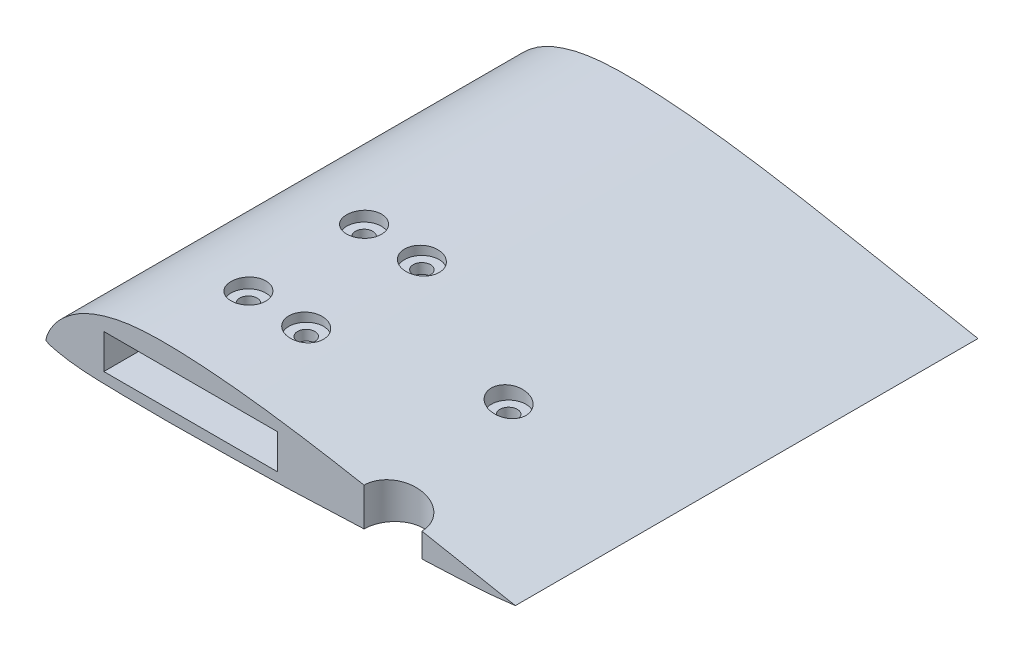
SolidWorks part; units mm, degrees
ref_plane "Front Plane" through (0, 0, 0) normal (0, 0, 1) x (1, 0, 0)
ref_plane "Top Plane" through (0, 0, 0) normal (0, 1, 0) x (1, 0, 0)
ref_plane "Right Plane" through (0, 0, 0) normal (1, 0, 0) x (0, 0, -1)
sketch "Sketch1" plane through (0, 0, 0) normal (0, 0, 1) x (1, 0, 0)
  line L0 (-18.4254, -0.1994) -> (62.7428, 0.679) construction
  line L1 (0, 9.7117) -> (0, -1.7957) construction
  line L2 (0, 9.741) -> (57.212, 9.741) construction
  line L3 (-32.1621, -1.8069) -> (66.409, -1.8069) construction
  spline S0 degree 3 poles (-18.4254, -0.1994) (-18.2508, -0.3232) (-18.0613, -0.4258) (-17.6702, -0.5885) (-17.4657, -0.6456) (-17.0528, -0.749) (-16.8454, -0.7957) (-16.4304, -0.8873) (-16.2225, -0.931) (-15.1812, -1.1388) (-14.3413, -1.2671) (-12.6506, -1.4595) (-11.8043, -1.5245) (-10.1107, -1.6203) (-9.2634, -1.6518) (-7.5684, -1.6982) (-6.7206, -1.7128) (-5.0249, -1.7383) (-4.1771, -1.7502) (-1.6335, -1.7827) (0.0625, -1.7998) (3.4549, -1.8108) (5.1508, -1.8016) (8.542, -1.7594) (10.2375, -1.7325) (13.6285, -1.6815) (15.3239, -1.6542) (18.7145, -1.5852) (20.4097, -1.5422) (25.4944, -1.3858) (28.8835, -1.2519) (33.967, -1.0399) (35.6612, -0.9657) (39.0492, -0.8072) (40.7428, -0.7213) (44.1297, -0.5456) (45.8232, -0.4567) (48.3639, -0.3343) (49.2109, -0.2955) (50.9053, -0.2226) (51.7526, -0.1878) (54.2939, -0.0756) (55.9876, 0.0095) (58.524, 0.2057) (59.3687, 0.2835) (61.0566, 0.4667) (61.8999, 0.5704) (62.7428, 0.679) knots 0 0 0 0 0.007813 0.007813 0.015625 0.015625 0.023438 0.023438 0.03125 0.03125 0.0625 0.0625 0.09375 0.09375 0.125 0.125 0.15625 0.15625 0.1875 0.1875 0.25 0.25 0.3125 0.3125 0.375 0.375 0.4375 0.4375 0.5 0.5 0.625 0.625 0.6875 0.6875 0.75 0.75 0.8125 0.8125 0.84375 0.84375 0.875 0.875 0.9375 0.9375 0.96875 0.96875 1 1 1 1
  spline S1 degree 3 poles (62.7428, 0.679) (59.228, 1.3467) (55.713, 2.013) (48.6835, 3.3493) (45.1699, 4.023) (38.1396, 5.3544) (34.6234, 6.0144) (27.5735, 7.2391) (24.0376, 7.8013) (16.9447, 8.7559) (13.3876, 9.1503) (8.0325, 9.5463) (6.2468, 9.646) (2.6732, 9.7541) (0.8855, 9.763) (-1.7993, 9.6315) (-2.6938, 9.5629) (-4.4662, 9.3564) (-5.3455, 9.2179) (-7.0877, 8.8546) (-7.9506, 8.6308) (-9.2314, 8.2238) (-9.6572, 8.0759) (-10.4962, 7.7567) (-11.3226, 7.4137) (-12.1183, 7.0123) (-12.8953, 6.5754) (-13.2746, 6.3395) (-14.0157, 5.8346) (-14.3793, 5.5647) (-15.0778, 4.9993) (-15.4131, 4.703) (-16.0517, 4.0791) (-16.3556, 3.752) (-16.9211, 3.0566) (-17.1818, 2.684) (-17.5376, 2.1057) (-17.6507, 1.9099) (-17.8667, 1.5129) (-17.9691, 1.3114) (-18.1538, 0.8974) (-18.2363, 0.6841) (-18.3633, 0.2503) (-18.4082, 0.0288) (-18.4254, -0.1994) knots 0 0 0 0 0.125 0.125 0.25 0.25 0.375 0.375 0.5 0.5 0.625 0.625 0.6875 0.6875 0.75 0.75 0.78125 0.78125 0.8125 0.8125 0.84375 0.84375 0.859375 0.859375 0.875 0.890625 0.890625 0.90625 0.90625 0.921875 0.921875 0.9375 0.9375 0.953125 0.953125 0.96875 0.96875 0.976562 0.976562 0.984375 0.984375 0.992188 0.992188 1 1 1 1
  point P4 (0, 0)
  dimension "D1" = 81.1682
  dimension "D2" = 11.5074
extrude "Boss-Extrude1" add sketch "Sketch1" along normal blind 80
sketch "Sketch2" plane through (0, 0, 80) normal (0, 0, 1) x (1, 0, 0)
  line L0 (-35.2815, 9.741) -> (70.1163, 9.741) construction
  line L1 (-36.5718, -1.8069) -> (68.6648, -1.8069) construction
  line L2 (-20.4254, 9.741) -> (-20.4254, -1.8069) construction
  line L3 (-8.4254, 9.741) -> (-8.4254, -1.6748) construction
  line L4 (-18.4254, -0.1994) -> (-20.4254, -0.1994) construction
  line L5 (-8.4254, 6.1531) -> (-8.4254, 0.1531)
  line L6 (-8.4254, 6.1531) -> (21.5746, 6.1531)
  line L7 (-8.4254, 0.1531) -> (21.5746, 0.1531)
  line L8 (21.5746, 6.1531) -> (21.5746, 0.1531)
  spline S2 degree 3 poles (552.4176, -2863.2339) (715.2007, -106.4952) (382.2094, -60.0531) (48.6835, 3.3493) (45.1699, 4.023) (38.1396, 5.3544) (34.6234, 6.0144) (27.5735, 7.2391) (24.0376, 7.8013) (16.9447, 8.7559) (13.3876, 9.1503) (8.0325, 9.5463) (6.2468, 9.646) (2.6732, 9.7541) (0.8855, 9.763) (-1.7993, 9.6315) (-2.6938, 9.5629) (-4.4662, 9.3564) (-5.3455, 9.2179) (-7.0877, 8.8546) (-7.9506, 8.6308) (-9.2314, 8.2238) (-9.6572, 8.0759) (-10.4962, 7.7567) (-11.3226, 7.4137) (-12.1183, 7.0123) (-12.8953, 6.5754) (-13.2746, 6.3395) (-14.0157, 5.8346) (-14.3793, 5.5647) (-15.0778, 4.9993) (-15.4131, 4.703) (-16.0517, 4.0791) (-16.3556, 3.752) (-16.9211, 3.0566) (-17.1818, 2.684) (-17.5376, 2.1057) (-17.6507, 1.9099) (-17.8667, 1.5129) (-17.9691, 1.3114) (-18.1538, 0.8974) (-18.2363, 0.6841) (-22.5005, -13.8816) (54.4548, -48.0097) (2883.2922, -752.8251) knots -11.611785 -11.611785 -11.611785 -11.611785 0.125 0.125 0.25 0.25 0.375 0.375 0.5 0.5 0.625 0.625 0.6875 0.6875 0.75 0.75 0.78125 0.78125 0.8125 0.8125 0.84375 0.84375 0.859375 0.859375 0.875 0.890625 0.890625 0.90625 0.90625 0.921875 0.921875 0.9375 0.9375 0.953125 0.953125 0.96875 0.96875 0.976562 0.976562 0.984375 0.984375 0.992188 0.992188 1.508965 1.508965 1.508965 1.508965 only from (62.7428, 0.679) to (-18.4254, -0.1994)
  spline S3 degree 3 poles (2965.539, 287.966) (-16.419, 111.793) (-31.3471, 5.1013) (-17.6702, -0.5885) (-17.4657, -0.6456) (-17.0528, -0.749) (-16.8454, -0.7957) (-16.4304, -0.8873) (-16.2225, -0.931) (-15.1812, -1.1388) (-14.3413, -1.2671) (-12.6506, -1.4595) (-11.8043, -1.5245) (-10.1107, -1.6203) (-9.2634, -1.6518) (-7.5684, -1.6982) (-6.7206, -1.7128) (-5.0249, -1.7383) (-4.1771, -1.7502) (-1.6335, -1.7827) (0.0625, -1.7998) (3.4549, -1.8108) (5.1508, -1.8016) (8.542, -1.7594) (10.2375, -1.7325) (13.6285, -1.6815) (15.3239, -1.6542) (18.7145, -1.5852) (20.4097, -1.5422) (25.4944, -1.3858) (28.8835, -1.2519) (33.967, -1.0399) (35.6612, -0.9657) (39.0492, -0.8072) (40.7428, -0.7213) (44.1297, -0.5456) (45.8232, -0.4567) (48.3639, -0.3343) (49.2109, -0.2955) (50.9053, -0.2226) (51.7526, -0.1878) (54.2939, -0.0756) (55.9876, 0.0095) (58.524, 0.2057) (59.3687, 0.2835) (124.5962, 7.3644) (184.8556, 84.629) (429.0917, -2973.0291) knots -0.530835 -0.530835 -0.530835 -0.530835 0.007813 0.007813 0.015625 0.015625 0.023438 0.023438 0.03125 0.03125 0.0625 0.0625 0.09375 0.09375 0.125 0.125 0.15625 0.15625 0.1875 0.1875 0.25 0.25 0.3125 0.3125 0.375 0.375 0.4375 0.4375 0.5 0.5 0.625 0.625 0.6875 0.6875 0.75 0.75 0.8125 0.8125 0.84375 0.84375 0.875 0.875 0.9375 0.9375 0.96875 0.96875 3.352794 3.352794 3.352794 3.352794 only from (-18.4254, -0.1994) to (62.7428, 0.679)
  spline S4 degree 3 poles (62.7428, 0.679) (59.228, 1.3467) (55.713, 2.013) (48.6835, 3.3493) (45.1699, 4.023) (38.1396, 5.3544) (34.6234, 6.0144) (27.5735, 7.2391) (24.0376, 7.8013) (16.9447, 8.7559) (13.3876, 9.1503) (8.0325, 9.5463) (6.2468, 9.646) (2.6732, 9.7541) (0.8855, 9.763) (-1.7993, 9.6315) (-2.6938, 9.5629) (-4.4662, 9.3564) (-5.3455, 9.2179) (-7.0877, 8.8546) (-7.9506, 8.6308) (-9.2314, 8.2238) (-9.6572, 8.0759) (-10.4962, 7.7567) (-11.3226, 7.4137) (-12.1183, 7.0123) (-12.8953, 6.5754) (-13.2746, 6.3395) (-14.0157, 5.8346) (-14.3793, 5.5647) (-15.0778, 4.9993) (-15.4131, 4.703) (-16.0517, 4.0791) (-16.3556, 3.752) (-16.9211, 3.0566) (-17.1818, 2.684) (-17.5376, 2.1057) (-17.6507, 1.9099) (-17.8667, 1.5129) (-17.9691, 1.3114) (-18.1538, 0.8974) (-18.2363, 0.6841) (-18.3633, 0.2503) (-18.4082, 0.0288) (-18.4254, -0.1994) knots 0 0 0 0 0.125 0.125 0.25 0.25 0.375 0.375 0.5 0.5 0.625 0.625 0.6875 0.6875 0.75 0.75 0.78125 0.78125 0.8125 0.8125 0.84375 0.84375 0.859375 0.859375 0.875 0.890625 0.890625 0.90625 0.90625 0.921875 0.921875 0.9375 0.9375 0.953125 0.953125 0.96875 0.96875 0.976562 0.976562 0.984375 0.984375 0.992188 0.992188 1 1 1 1
  spline S5 degree 3 poles (-18.4254, -0.1994) (-18.2508, -0.3232) (-18.0613, -0.4258) (-17.6702, -0.5885) (-17.4657, -0.6456) (-17.0528, -0.749) (-16.8454, -0.7957) (-16.4304, -0.8873) (-16.2225, -0.931) (-15.1812, -1.1388) (-14.3413, -1.2671) (-12.6506, -1.4595) (-11.8043, -1.5245) (-10.1107, -1.6203) (-9.2634, -1.6518) (-7.5684, -1.6982) (-6.7206, -1.7128) (-5.0249, -1.7383) (-4.1771, -1.7502) (-1.6335, -1.7827) (0.0625, -1.7998) (3.4549, -1.8108) (5.1508, -1.8016) (8.542, -1.7594) (10.2375, -1.7325) (13.6285, -1.6815) (15.3239, -1.6542) (18.7145, -1.5852) (20.4097, -1.5422) (25.4944, -1.3858) (28.8835, -1.2519) (33.967, -1.0399) (35.6612, -0.9657) (39.0492, -0.8072) (40.7428, -0.7213) (44.1297, -0.5456) (45.8232, -0.4567) (48.3639, -0.3343) (49.2109, -0.2955) (50.9053, -0.2226) (51.7526, -0.1878) (54.2939, -0.0756) (55.9876, 0.0095) (58.524, 0.2057) (59.3687, 0.2835) (61.0566, 0.4667) (61.8999, 0.5704) (62.7428, 0.679) knots 0 0 0 0 0.007813 0.007813 0.015625 0.015625 0.023438 0.023438 0.03125 0.03125 0.0625 0.0625 0.09375 0.09375 0.125 0.125 0.15625 0.15625 0.1875 0.1875 0.25 0.25 0.3125 0.3125 0.375 0.375 0.4375 0.4375 0.5 0.5 0.625 0.625 0.6875 0.6875 0.75 0.75 0.8125 0.8125 0.84375 0.84375 0.875 0.875 0.9375 0.9375 0.96875 0.96875 1 1 1 1
  point P10 (-8.4254, 8.4766)
  dimension "D2" = 2
  dimension "D3" = 12
  dimension "D4" = 6
  dimension "D5" = 30
  dimension "D1" = 0
extrude "Cut-Extrude1" cut sketch "Sketch2" against normal blind 65 contours L8 L6 L5 L7 region at (6.5746, 3.1531, 80)
ref_plane "Plane1" through (0, 9.9139, 0) normal (0, -1, 0) x (-1, 0, 0)
sketch "Sketch4" plane through (0, 9.9139, 0) normal (0, -1, 0) x (-1, 0, 0)
  line L0 (18.4254, 0) -> (-62.7428, 0)
  line L1 (-62.7428, 0) -> (-62.7428, -80)
  line L2 (-62.7428, -80) -> (18.4254, -80) construction
  line L3 (18.4254, -80) -> (18.4254, 0) construction
  line L4 (-1.5746, 0) -> (-1.5746, -45) construction
  circle A0 centre (-1.5746, -45) radius 3
  circle A1 centre (-11.5746, -45) radius 3
  circle A2 centre (-11.5746, -65) radius 3
  circle A3 centre (-1.5746, -65) radius 3
  point P0 (18.4254, 0)
  point P1 (-62.7428, 0)
  point P3 (-62.7428, -80)
  point P5 (18.4254, -80)
  dimension "D3" = 6
  dimension "D4" = 2
  dimension "D1" = 45
  dimension "D2" = 20
  dimension "D5" = 2
extrude "Cut-Extrude2" cut sketch "Sketch4" along normal blind 2 contours A0 | A1 | A2 | A3 region at (1.5746, 9.9139, 45) region at (11.5746, 9.9139, 45) region at (11.5746, 9.9139, 65) region at (1.5746, 9.9139, 65)
sketch "Sketch5" plane through (0, 7.9139, 0) normal (0, 1, 0) x (1, 0, 0)
  circle A0 centre (1.5746, -65) radius 3 construction
  circle A1 centre (11.5746, -65) radius 3 construction
  circle A2 centre (11.5746, -45) radius 3 construction
  circle A3 centre (1.5746, -45) radius 3 construction
  circle A4 centre (1.5746, -65) radius 3
  circle A5 centre (11.5746, -65) radius 3
  circle A6 centre (11.5746, -45) radius 3
  circle A7 centre (1.5746, -45) radius 3
  circle A8 centre (1.5746, -45) radius 1.5
  circle A9 centre (11.5746, -45) radius 1.5
  circle A10 centre (11.5746, -65) radius 1.5
  circle A11 centre (1.5746, -65) radius 1.5
  dimension "D1" = 3
  dimension "D2" = 2
  dimension "D3" = 2
extrude "Cut-Extrude3" cut sketch "Sketch5" against normal through all contours A8 | A9 | A10 | A11 region at (1.5746, 7.9139, 45) region at (11.5746, 7.9139, 45) region at (11.5746, 7.9139, 65) region at (1.5746, 7.9139, 65)
ref_plane "Plane2" through (0, 6.2531, 0) normal (0, -1, 0) x (-1, 0, 0)
sketch "Sketch6" plane through (0, 6.2531, 0) normal (0, -1, 0) x (-1, 0, 0)
  line L0 (-11.5746, -45) -> (-11.5746, -65) construction
  line L1 (-11.5746, -55) -> (-33.5746, -55) construction
  line L2 (18.4254, -80) -> (18.4254, 0) construction
  circle A0 centre (-1.5746, -65) radius 1.5 construction
  circle A1 centre (-11.5746, -65) radius 1.5 construction
  circle A2 centre (-11.5746, -45) radius 1.5 construction
  circle A3 centre (-1.5746, -45) radius 1.5 construction
  circle A4 centre (-1.5746, -65) radius 1.5
  circle A5 centre (-11.5746, -65) radius 1.5
  circle A6 centre (-11.5746, -45) radius 1.5
  circle A7 centre (-1.5746, -45) radius 1.5
  circle A8 centre (-36.5746, -55) radius 3
  dimension "D2" = 6
  dimension "D1" = 22
  dimension "D3" = 52
extrude "Cut-Extrude4" cut sketch "Sketch6" along normal blind 2.5 contours A8
sketch "Sketch7" plane through (0, 3.7531, 0) normal (0, 1, 0) x (1, 0, 0)
  circle A0 centre (36.5746, -55) radius 1.5
  circle A1 centre (36.5746, -55) radius 3
  circle A2 centre (36.5746, -55) radius 3 construction
  dimension "D2" = 3
  dimension "D1" = 0
extrude "Cut-Extrude5" cut sketch "Sketch7" against normal through all
sketch "Sketch9" plane through (0, 9.9139, 0) normal (0, -1, 0) x (-1, 0, 0)
  line L0 (-62.7428, -80) -> (18.4254, -80) construction
  line L1 (-62.7428, -80) -> (18.4254, -80)
  circle A0 centre (-41.5746, -80) radius 5
  point P2 (-41.5746, -80)
  dimension "D2" = 10
  dimension "D1" = 60
extrude "Cut-Extrude7" cut sketch "Sketch9" along normal through all contours L1 A0 | L1 A0 region at (41.5746, 9.9139, 77.8779) region at (41.5746, 9.9139, 82.1221)
